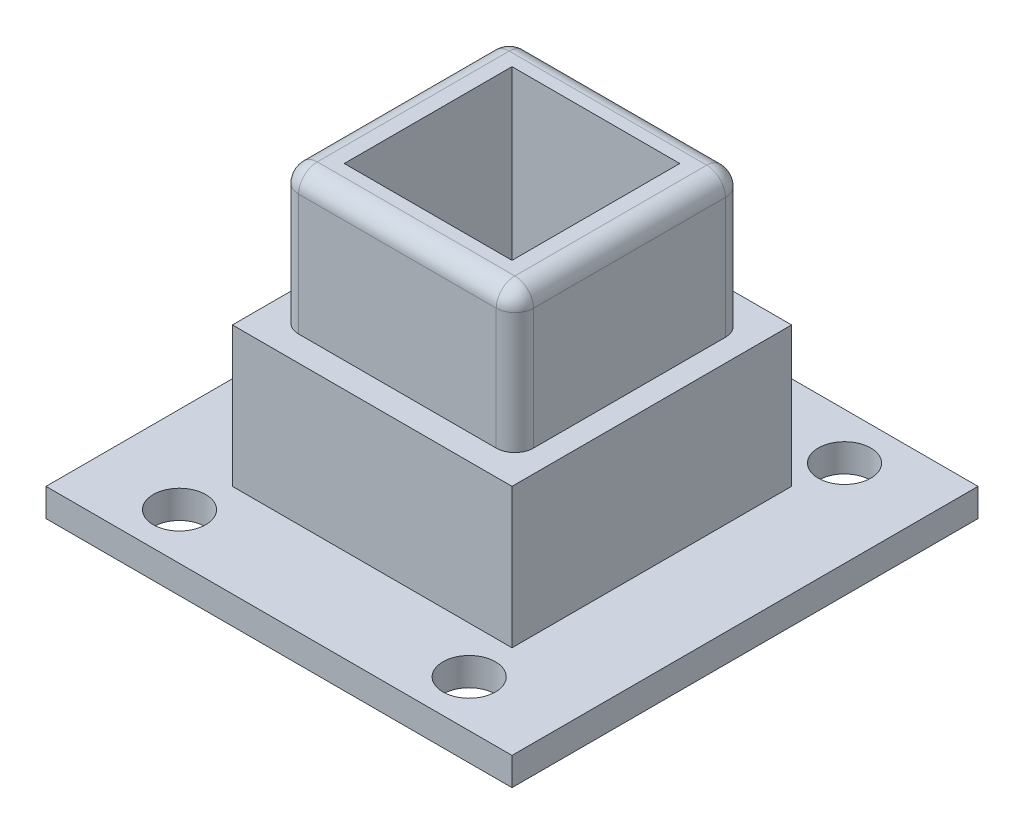
SolidWorks part; units mm, degrees
ref_plane "Alzado" through (0, 0, 0) normal (0, 0, 1) x (1, 0, 0)
ref_plane "Planta" through (0, 0, 0) normal (0, 1, 0) x (1, 0, 0)
ref_plane "Vista lateral" through (0, 0, 0) normal (1, 0, 0) x (0, 0, -1)
sketch "Croquis1" plane through (0, 0, 0) normal (0, 1, 0) x (1, 0, 0)
  line L1 (-25, 25) -> (25, 25)
  line L2 (-25, 25) -> (-25, -25)
  line L3 (-25, -25) -> (25, -25)
  line L4 (25, 25) -> (25, -25)
  line L5 (-25, 25) -> (25, -25) construction
  line L6 (-25, -25) -> (25, 25) construction
  point P0 (0, 0)
  dimension "D1" = 50
  dimension "D2" = 50
extrude "Saliente-Extruir1" add sketch "Croquis1" along normal blind 3
sketch "Croquis2" plane through (0, 3, 0) normal (0, 1, 0) x (1, 0, 0)
  line L1 (-15, 15) -> (15, 15)
  line L2 (-15, 15) -> (-15, -15)
  line L3 (-15, -15) -> (15, -15)
  line L4 (15, 15) -> (15, -15)
  line L5 (-15, 15) -> (15, -15) construction
  line L6 (-15, -15) -> (15, 15) construction
  line L7 (-9, 9) -> (9, 9)
  line L8 (-9, 9) -> (-9, -9)
  line L9 (-9, -9) -> (9, -9)
  line L10 (9, 9) -> (9, -9)
  line L11 (-9, 9) -> (9, -9) construction
  line L12 (-9, -9) -> (9, 9) construction
  point P0 (0, 0)
  point P6 (0, 0)
  dimension "D1" = 30
  dimension "D2" = 30
  dimension "D3" = 6
extrude "Saliente-Extruir2" add sketch "Croquis2" along normal blind 30
sketch "Croquis3" plane through (0, 3, 0) normal (0, 1, 0) x (1, 0, 0)
  line L0 (25, -20) -> (-25, -20) construction
  line L1 (25, -25) -> (25, 25) construction
  line L2 (-25, 25) -> (-25, -25) construction
  line L3 (25, 20) -> (-25, 20) construction
  line L4 (0, -25) -> (0, -15) construction
  line L5 (-25, -25) -> (25, -25) construction
  line L6 (-15, -15) -> (15, -15) construction
  line L7 (0, 15) -> (0, 25) construction
  line L8 (15, 15) -> (-15, 15) construction
  line L9 (25, 25) -> (-25, 25) construction
  line L10 (15.6762, -25) -> (15.6762, 25) construction
  line L11 (-15.6762, -25) -> (-15.6762, 25) construction
  circle A0 centre (15.4054, -20) radius 2.8139
  circle A1 centre (-15.6762, -20) radius 2.8139
  circle A2 centre (15.6762, 20) radius 2.8139
  circle A3 centre (-15.6762, 20) radius 2.8139
  point P22 (0, -20)
  point P29 (0, 20)
extrude "Cortar-Extruir1" cut sketch "Croquis3" against normal blind 10
sketch "Croquis4" plane through (0, 33, 0) normal (0, 1, 0) x (1, 0, 0)
  line L0 (-9, 9) -> (-9, -9) construction
  line L1 (15, -15) -> (-15, -15)
  line L2 (15, -15) -> (15, 15)
  line L3 (15, 15) -> (-15, 15)
  line L4 (-15, -15) -> (-15, 15)
  line L5 (12.6, -12.2932) -> (-12.6, -12.2932)
  line L6 (12.6, -12.2932) -> (12.6, 12.2932)
  line L7 (12.6, 12.2932) -> (-12.6, 12.2932)
  line L8 (-12.6, -12.2932) -> (-12.6, 12.2932)
  line L9 (12.6, -12.2932) -> (-12.6, 12.2932) construction
  line L10 (12.6, 12.2932) -> (-12.6, -12.2932) construction
  point P6 (0, 0)
  dimension "D1" = 3.6
extrude "Cortar-Extruir2" cut sketch "Croquis4" against normal blind 15
fillet "Redondeo1" radius 2 8 edges at (0, 33, 12.2932) (-12.6, 25.5, 12.2932) (-12.6, 33, 0) (-12.6, 25.5, -12.2932) (0, 33, -12.2932) (12.6, 33, 0) (12.6, 25.5, -12.2932) (12.6, 25.5, 12.2932)
